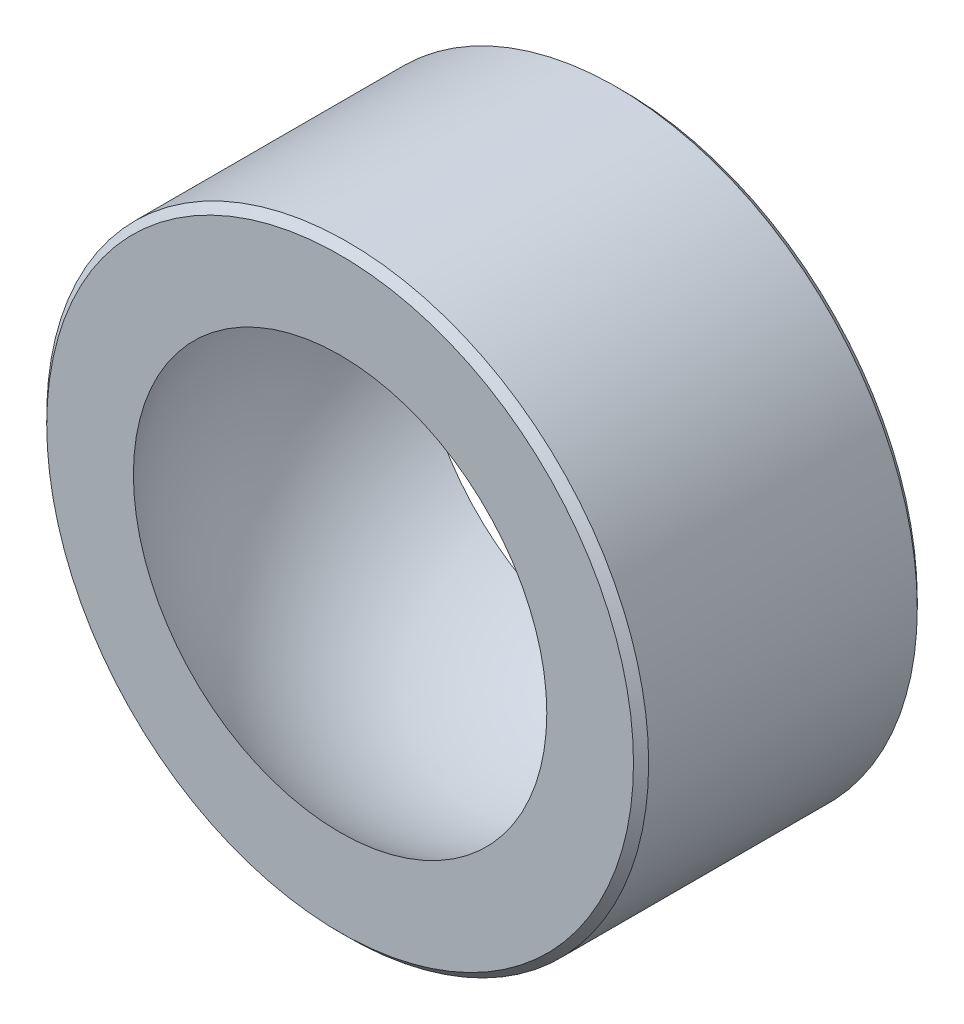
SolidWorks part; units mm, degrees
material "AISI 4130 Steel, normalized at 870C"
ref_plane "Front Plane" through (0, 0, 0) normal (0, 0, 1) x (1, 0, 0)
ref_plane "Top Plane" through (0, 0, 0) normal (0, 1, 0) x (1, 0, 0)
ref_plane "Right Plane" through (0, 0, 0) normal (1, 0, 0) x (0, 0, -1)
sketch "Sketch1" plane through (0, 0, 0) normal (0, 0, 1) x (1, 0, 0)
  circle A0 centre (0, 0) radius 11.9062
  dimension "D1" = 23.8125
extrude "Boss-Extrude1" add sketch "Sketch1" along normal blind 5.6134 and the other way blind 5.6134
sketch "Sketch2" plane through (0, 0, 0) normal (0, 0, 1) x (1, 0, 0)
  line L0 (0, 9.9187) -> (0, -9.9187)
  line L1 (0, 12.923) -> (0, -12.923) construction
  arc A0 (0, -9.9187) -> (0, 9.9187) centre (0, 0) ccw
  dimension "D1" = 9.9187
sketch "Sketch3" plane through (0, 0, 0) normal (0, 1, 0) x (1, 0, 0)
  line L1 (-12.6092, 4.5) -> (12.6092, 4.5)
  line L2 (-12.6092, 4.5) -> (-12.6092, -4.5)
  line L3 (-12.6092, -4.5) -> (12.6092, -4.5)
  line L4 (12.6092, 4.5) -> (12.6092, -4.5)
  line L5 (-12.6092, 4.5) -> (12.6092, -4.5) construction
  line L6 (-12.6092, -4.5) -> (12.6092, 4.5) construction
  point P0 (0, 0)
  dimension "D1" = 4.5
extrude "Cut-Extrude1" [suppressed] cut sketch "Sketch3" against normal through all and the other way through all flip side to cut
sketch "Sketch4" plane through (0, 0, 0) normal (0, 0, 1) x (1, 0, 0)
  circle A0 centre (0, 0) radius 5
  dimension "D1" = 10
extrude "Cut-Extrude2" [suppressed] cut sketch "Sketch4" against normal through all and the other way through all
revolve "Cut-Revolve1" cut sketch "Sketch2" angle 360 about L1
chamfer "Chamfer1" distance 0.3 angle 45 2 edges at (11.9062, 0, 5.6134) (11.9062, 0, -5.6134)
